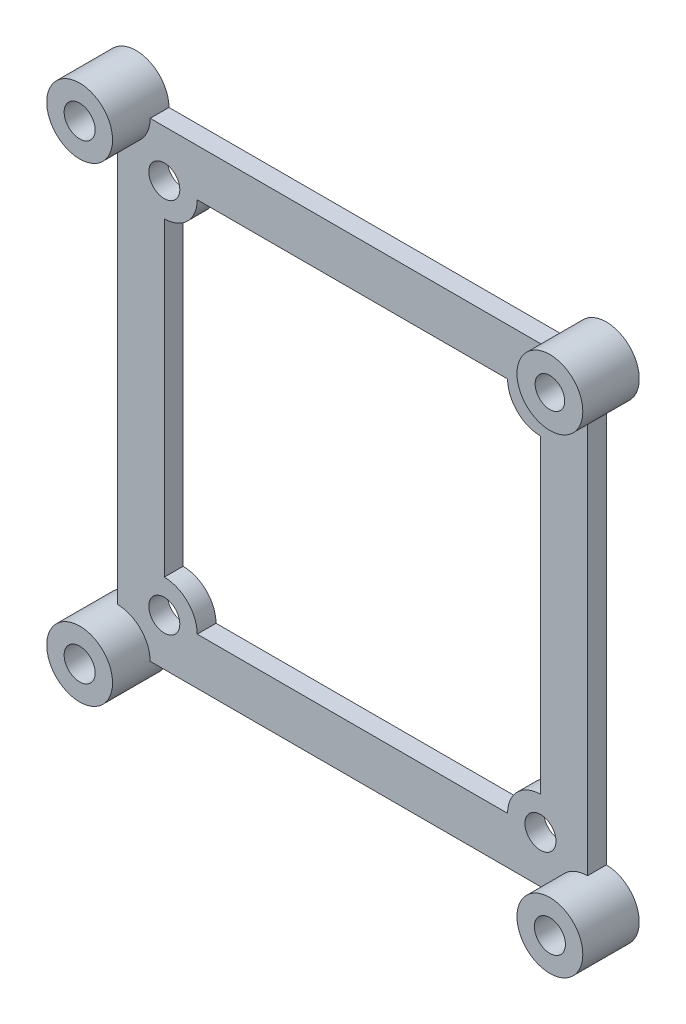
SolidWorks part; units mm, degrees
ref_plane "Front Plane" through (0, 0, 0) normal (0, 0, 1) x (1, 0, 0)
ref_plane "Top Plane" through (0, 0, 0) normal (0, 1, 0) x (1, 0, 0)
ref_plane "Right Plane" through (0, 0, 0) normal (1, 0, 0) x (0, 0, -1)
sketch "Sketch1" plane through (0, 0, 0) normal (0, 0, 1) x (1, 0, 0)
  line L0 (-16.5, 20) -> (16.5, 20)
  line L1 (20, 20) -> (-20, 20) construction
  line L2 (20, 20) -> (20, -20) construction
  line L3 (20, -20) -> (-20, -20) construction
  line L4 (-20, 20) -> (-20, -20) construction
  line L5 (20, 20) -> (-20, -20) construction
  line L6 (20, -20) -> (-20, 20) construction
  line L7 (25, 25) -> (-25, 25) construction
  line L8 (25, 25) -> (25, -25) construction
  line L9 (25, -25) -> (-25, -25) construction
  line L10 (-25, 25) -> (-25, -25) construction
  line L11 (25, 25) -> (-25, -25) construction
  line L12 (25, -25) -> (-25, 25) construction
  line L13 (-20, 16.5) -> (-20, -16.5)
  line L14 (-16.5, -20) -> (16.5, -20)
  line L15 (20, 16.5) -> (20, -16.5)
  line L16 (-21.5, 25) -> (21.5, 25)
  line L17 (25, 21.5) -> (25, -21.5)
  line L18 (-25, 21.5) -> (-25, -21.5)
  line L19 (-21.5, -25) -> (21.5, -25)
  circle A0 centre (-20, 20) radius 1.65
  circle A1 centre (-25, 25) radius 1.65
  circle A2 centre (20, 20) radius 1.65
  circle A3 centre (25, 25) radius 1.65
  circle A4 centre (25, -25) radius 1.65
  circle A5 centre (20, -20) radius 1.65
  circle A6 centre (-20, -20) radius 1.65
  circle A7 centre (-25, -25) radius 1.65
  arc A8 (-21.5, 25) -> (-25, 21.5) centre (-25, 25) ccw
  arc A9 (-20, 16.5) -> (-16.5, 20) centre (-20, 20) ccw
  arc A10 (16.5, 20) -> (20, 16.5) centre (20, 20) ccw
  arc A11 (25, 21.5) -> (21.5, 25) centre (25, 25) ccw
  arc A12 (21.5, -25) -> (25, -21.5) centre (25, -25) ccw
  arc A13 (20, -16.5) -> (16.5, -20) centre (20, -20) ccw
  arc A14 (-16.5, -20) -> (-20, -16.5) centre (-20, -20) ccw
  arc A15 (-25, -21.5) -> (-21.5, -25) centre (-25, -25) ccw
  point P0 (0, 0)
  point P6 (0, 0)
  dimension "D5" = 3.3
  dimension "D6" = 7
  dimension "D1" = 50
  dimension "D2" = 50
  dimension "D3" = 40
  dimension "D4" = 40
extrude "Boss-Extrude1" add sketch "Sketch1" along normal blind 2
sketch "Sketch2" plane through (0, 0, 2) normal (0, 0, 1) x (1, 0, 0)
  circle A0 centre (-25, 25) radius 1.65
  circle A1 centre (-25, 25) radius 3.5
  circle A2 centre (25, 25) radius 1.5707
  circle A3 centre (25, 25) radius 3.5
  circle A4 centre (-25, -25) radius 1.65
  circle A5 centre (-25, -25) radius 3.5
  circle A6 centre (25, -25) radius 1.65
  circle A7 centre (25, -25) radius 3.5
extrude "Boss-Extrude2" add sketch "Sketch2" along normal blind 4
